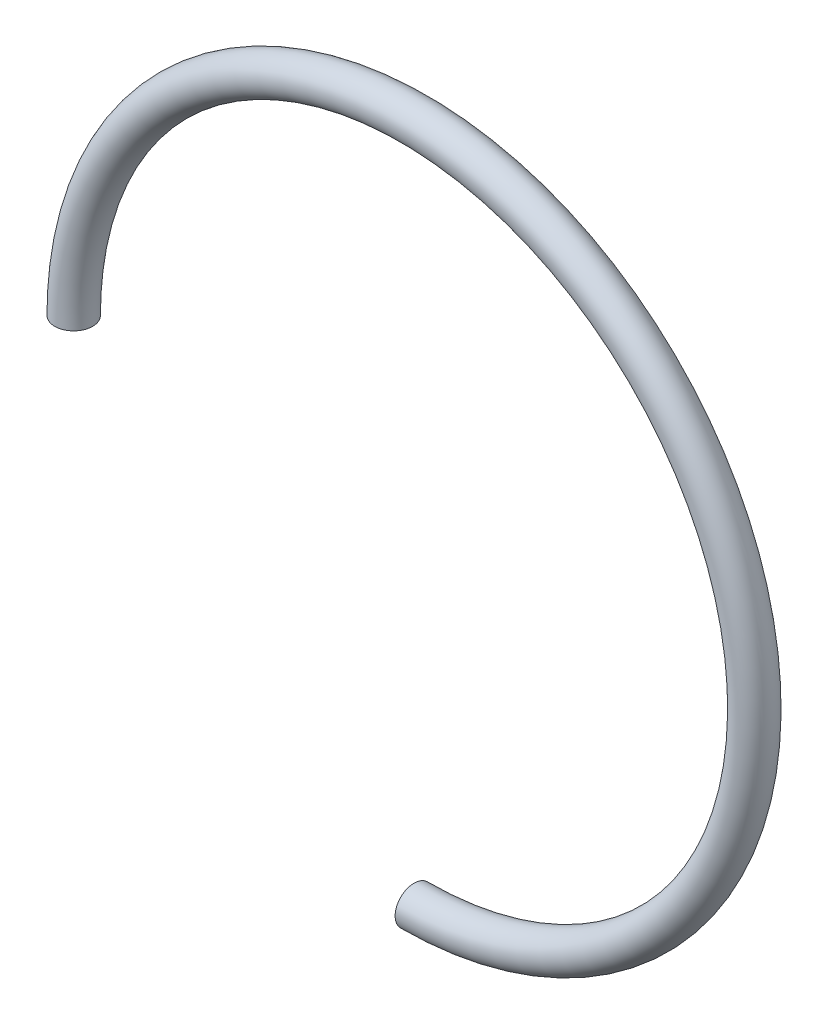
SolidWorks part; units mm, degrees
ref_plane "Plano frontal" through (0, 0, 0) normal (0, 0, 1) x (1, 0, 0)
ref_plane "Plano superior" through (0, 0, 0) normal (0, 1, 0) x (1, 0, 0)
ref_plane "Plano direito" through (0, 0, 0) normal (1, 0, 0) x (0, 0, -1)
sketch "Esboço1" plane through (0, 0, 0) normal (0, 0, 1) x (1, 0, 0)
  arc A0 (0, -4.5) -> (-4.5, 0) centre (0, 0) ccw
  dimension "D1" = 4.5
sweep "Varredura1" add path "Esboço1" circular profile diameter 0.5 parameters "D3"=0.5
